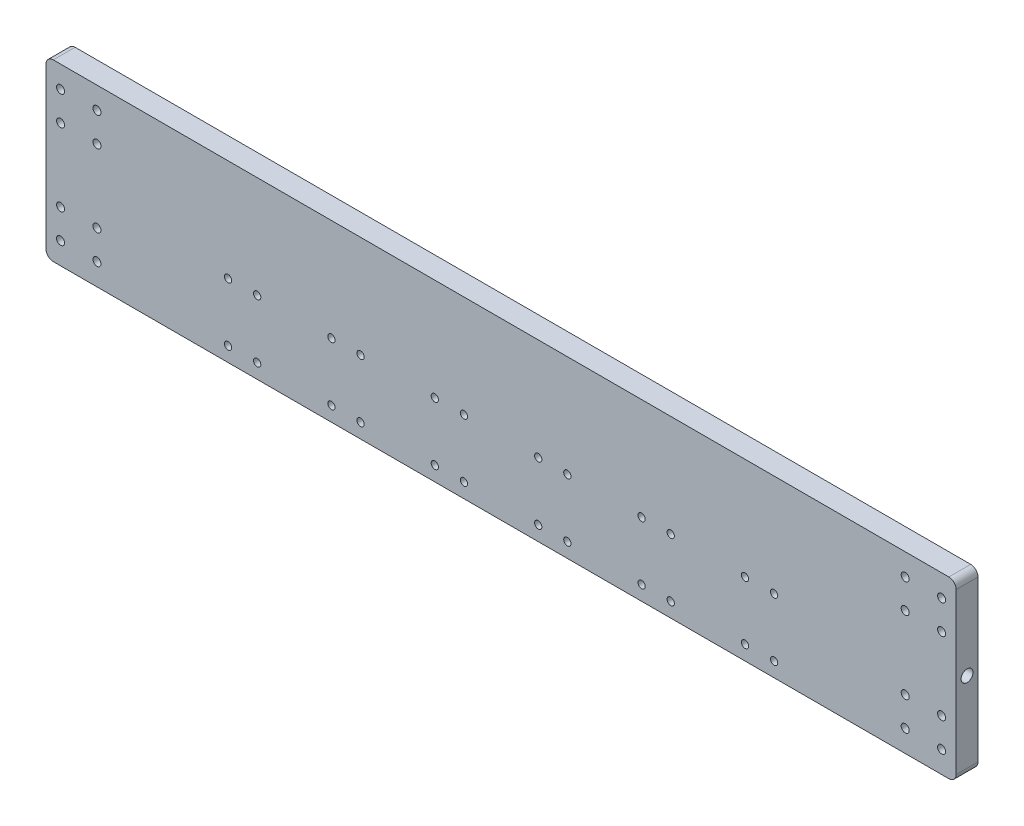
SolidWorks part; units mm, degrees
ref_plane "Plan de face" through (0, 0, 0) normal (0, 0, 1) x (1, 0, 0)
ref_plane "Plan de dessus" through (0, 0, 0) normal (0, 1, 0) x (1, 0, 0)
ref_plane "Plan de droite" through (0, 0, 0) normal (1, 0, 0) x (0, 0, -1)
sketch "Esquisse1" plane through (0, 0, 0) normal (0, 0, 1) x (1, 0, 0)
  line L1 (0, 0) -> (625, 0)
  line L2 (0, 0) -> (0, 120)
  line L3 (0, 120) -> (625, 120)
  line L4 (625, 0) -> (625, 120)
  dimension "D1" = 120
  dimension "D2" = 625
extrude "Boss.-Extru.1" add sketch "Esquisse1" along normal blind 15
sketch "Esquisse2" plane through (0, 0, 15) normal (0, 0, 1) x (1, 0, 0)
  line L0 (312.5, 0) -> (312.5, 120) construction
  line L1 (0, 0) -> (625, 0) construction
  line L2 (625, 120) -> (0, 120) construction
  line L3 (22.5, 120) -> (22.5, 0) construction
  line L4 (22.5, 60) -> (0, 60) construction
  line L5 (0, 120) -> (0, 0) construction
  line L6 (10, 105) -> (10, 85) construction
  line L7 (615, 105) -> (615, 85) construction
  line L8 (602.5, 60) -> (625, 60) construction
  line L9 (602.5, 120) -> (602.5, 0) construction
  circle A0 centre (10, 105) radius 2.75
  circle A1 centre (10, 85) radius 2.75
  circle A2 centre (35, 85) radius 2.75
  circle A3 centre (35, 105) radius 2.75
  circle A4 centre (35, 15) radius 2.75
  circle A5 centre (35, 35) radius 2.75
  circle A6 centre (10, 35) radius 2.75
  circle A7 centre (10, 15) radius 2.75
  circle A8 centre (615, 15) radius 2.75
  circle A9 centre (615, 35) radius 2.75
  circle A10 centre (590, 35) radius 2.75
  circle A11 centre (590, 15) radius 2.75
  circle A12 centre (590, 105) radius 2.75
  circle A13 centre (590, 85) radius 2.75
  circle A14 centre (615, 85) radius 2.75
  circle A15 centre (615, 105) radius 2.75
  dimension "D1" = 20
  dimension "D2" = 25
  dimension "D3" = 5.5
  dimension "D4" = 50
  dimension "D5" = 580
extrude "Enlèv. mat.-Extru.1" cut sketch "Esquisse2" against normal through all both and the other way through all
fillet "Congé1" radius 5 4 edges at (625, 120, 7.5) (625, 0, 7.5) (0, 0, 7.5) (0, 120, 7.5)
sketch "Esquisse3" plane through (625, 0, 0) normal (1, 0, 0) x (0, 0, -1)
  line L0 (-15, 60) -> (0, 60) construction
  line L1 (-15, 5) -> (-15, 115) construction
  line L2 (0, 5) -> (0, 115) construction
  circle A0 centre (-7.5, 60) radius 4.1
  dimension "D1" = 8.2
extrude "Enlèv. mat.-Extru.2" cut sketch "Esquisse3" against normal blind 20
extrude "Enlèv. mat.-Extru.3" cut sketch "Esquisse3<2>" along normal blind 20 from surface starting at face at (0, 60, 7.5)
sketch "Esquisse3<2>" plane through (625, 0, 0) normal (1, 0, 0) x (0, 0, -1) same geometry as "Esquisse3"
sketch "Esquisse4" plane through (0, 0, 15) normal (0, 0, 1) x (1, 0, 0)
  line L0 (0, 30) -> (625, 30) construction
  line L3 (312.5, 30) -> (312.5, 120) construction
  line L4 (620, 120) -> (5, 120) construction
  line L5 (277, 30) -> (277, 93.3675) construction
  line L6 (241.5, 30) -> (241.5, 112.952) construction
  line L7 (170.5, 30) -> (170.5, 101.3546) construction
  line L8 (0, 115) -> (0, 5) construction
  line L9 (5, 0) -> (620, 0) construction
  circle A0 centre (267, 50) radius 2.5
  circle A1 centre (287, 50) radius 2.5
  circle A2 centre (287, 10) radius 2.5
  circle A3 centre (267, 10) radius 2.5
  circle A4 centre (358, 10) radius 2.5
  circle A5 centre (338, 10) radius 2.5
  circle A6 centre (338, 50) radius 2.5
  circle A7 centre (358, 50) radius 2.5
  circle A8 centre (216, 10) radius 2.5
  circle A9 centre (196, 10) radius 2.5
  circle A10 centre (196, 50) radius 2.5
  circle A11 centre (216, 50) radius 2.5
  circle A12 centre (125, 50) radius 2.5
  circle A13 centre (145, 50) radius 2.5
  circle A14 centre (145, 10) radius 2.5
  circle A15 centre (125, 10) radius 2.5
  circle A16 centre (500, 10) radius 2.5
  circle A17 centre (480, 10) radius 2.5
  circle A18 centre (480, 50) radius 2.5
  circle A19 centre (500, 50) radius 2.5
  circle A20 centre (409, 50) radius 2.5
  circle A21 centre (429, 50) radius 2.5
  circle A22 centre (429, 10) radius 2.5
  circle A23 centre (409, 10) radius 2.5
  dimension "D1" = 5
  dimension "D2" = 20
  dimension "D3" = 40
  dimension "D4" = 35.5
  dimension "D5" = 71
  dimension "D6" = 71
  dimension "D7" = 30
extrude "Enlèv. mat.-Extru.4" cut sketch "Esquisse4" against normal through all both and the other way through all
